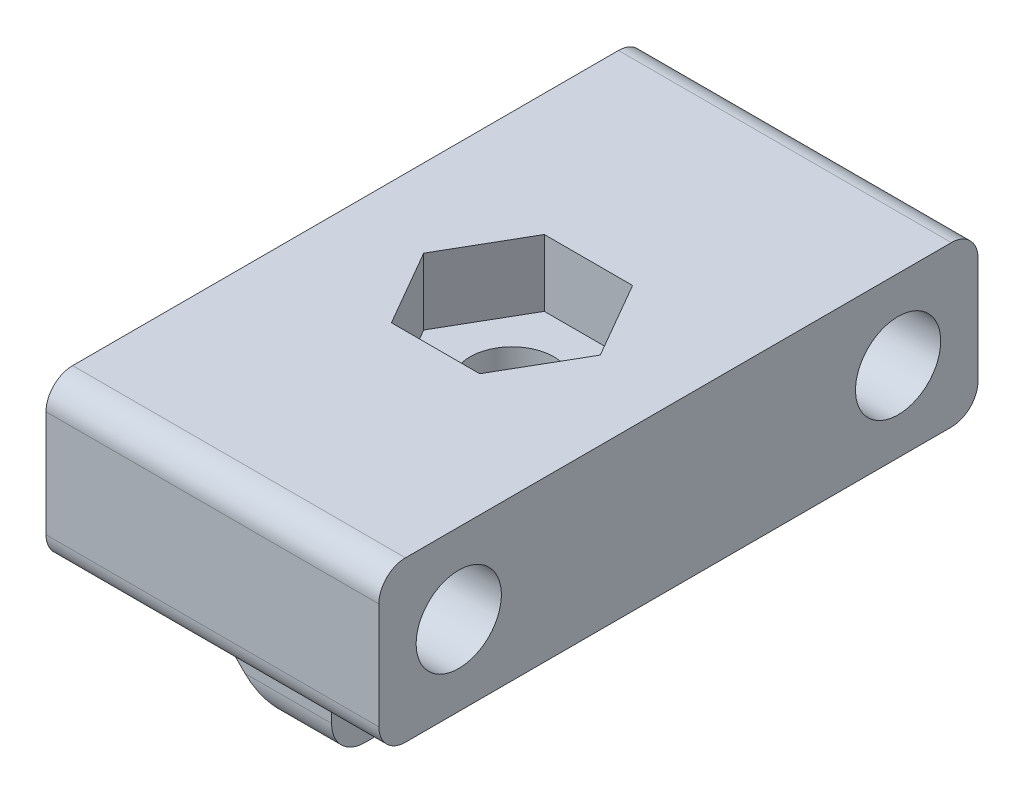
SolidWorks part; units mm, degrees
ref_plane "Front" through (0, 0, 0) normal (0, 0, 1) x (1, 0, 0)
ref_plane "Top" through (0, 0, 0) normal (0, 1, 0) x (1, 0, 0)
ref_plane "Right" through (0, 0, 0) normal (1, 0, 0) x (0, 0, -1)
sketch "Sketch1" plane through (0, 0, 0) normal (0, 1, 0) x (1, 0, 0)
  line L1 (12.5, -22.5) -> (-12.5, -22.5)
  line L2 (12.5, -22.5) -> (12.5, 22.5)
  line L3 (12.5, 22.5) -> (-12.5, 22.5)
  line L4 (-12.5, -22.5) -> (-12.5, 22.5)
  line L5 (12.5, -22.5) -> (-12.5, 22.5) construction
  line L6 (12.5, 22.5) -> (-12.5, -22.5) construction
  point P0 (0, 0)
  dimension "D1" = 45
  dimension "D2" = 25
extrude "Boss-Extrude1" add sketch "Sketch1" along normal blind 12
sketch "Sketch2" plane through (0, 12, 0) normal (0, 1, 0) x (1, 0, 0)
  line L1 (3.315, -5.7417) -> (6.63, 0)
  line L2 (6.63, 0) -> (3.315, 5.7417)
  line L3 (3.315, 5.7417) -> (-3.315, 5.7417)
  line L4 (-3.315, 5.7417) -> (-6.63, 0)
  line L5 (-6.63, 0) -> (-3.315, -5.7417)
  line L6 (-3.315, -5.7417) -> (3.315, -5.7417)
  circle A0 centre (0, 0) radius 5.7417 construction
  dimension "D1" = 6.63
extrude "Cut-Extrude1" cut sketch "Sketch2" against normal blind 5
sketch "Sketch3" plane through (0, 7, 0) normal (0, 1, 0) x (1, 0, 0)
  circle A0 centre (0, 0) radius 3.15
  dimension "D1" = 6.3
extrude "Cut-Extrude2" cut sketch "Sketch3" against normal through all
sketch "Sketch8" plane through (-12.5, 0, 0) normal (-1, 0, 0) x (0, 0, 1)
  line L0 (22.5, 12) -> (22.5, 0) construction
  circle A0 centre (16.5, 6) radius 3.2
  dimension "D1" = 6.4
  dimension "D2" = 6
extrude "Cut-Extrude5" cut sketch "Sketch8" against normal through all contours A0
mirror "Mirror1" about plane through (0, 0, 0) normal (0, 0, 1) of "Cut-Extrude5"
fillet "Fillet1" radius 2 4 edges at (0, 12, 22.5) (0, 0, 22.5) (0, 0, -22.5) (0, 12, -22.5)
sketch "Sketch10" plane through (0, 0, 0) normal (0, -1, 0) x (-1, 0, 0)
  line L1 (-5, -18.5499) -> (5, -18.5499)
  line L2 (-5, -18.5499) -> (-5, 18.5499)
  line L3 (-5, 18.5499) -> (5, 18.5499)
  line L4 (5, -18.5499) -> (5, 18.5499)
  line L5 (-5, -18.5499) -> (5, 18.5499) construction
  line L6 (-5, 18.5499) -> (5, -18.5499) construction
  line L7 (-5, 30.7042) -> (-5, 42.1799) construction
  point P0 (0, 0)
extrude "Boss-Extrude2" add sketch "Sketch10" along normal blind 6
chamfer "Chamfer1" distance 6 angle 45 1 edges at (-5, -6, 0)
fillet "Fillet2" radius 2.5 2 edges at (3, -6, -18.5499) (3, -6, 18.5499)
fillet "Fillet3" radius 1 2 edges at (0, 0, -18.5499) (0, 0, 18.5499)
sketch "Sketch12" plane through (0, 0, 0) normal (0, 1, 0) x (1, 0, 0)
  circle A0 centre (0, 0) radius 3.15
extrude "Cut-Extrude6" cut sketch "Sketch12" against normal blind 6
